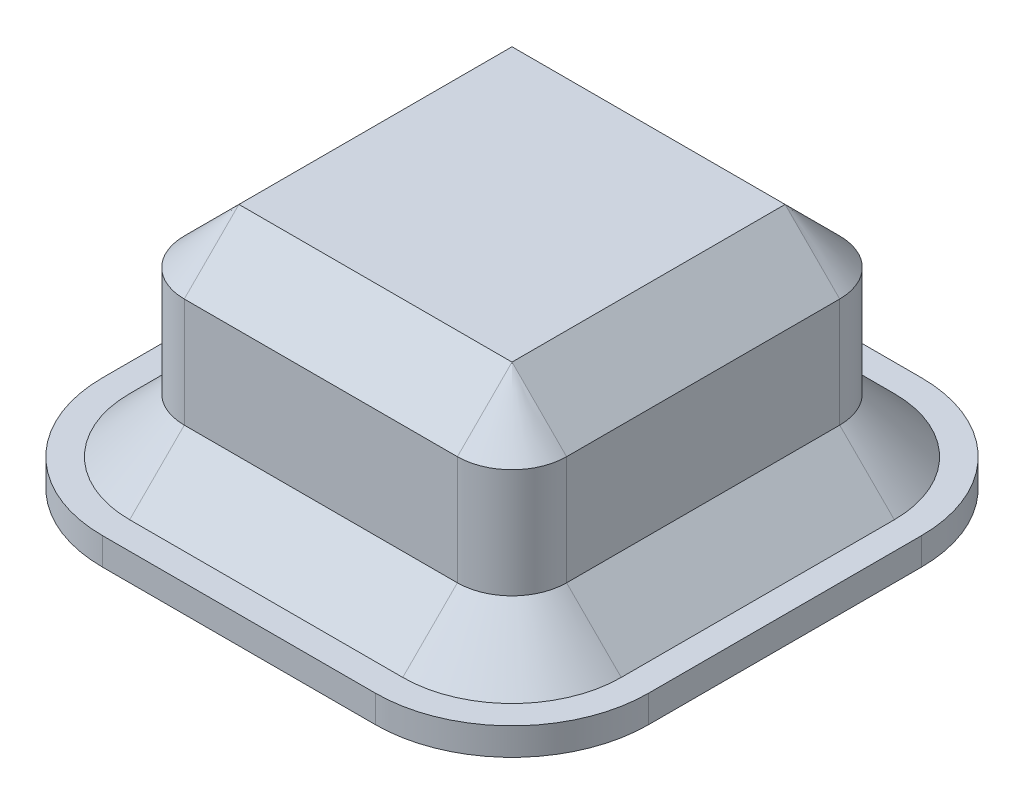
SolidWorks part; units mm, degrees
material "ABS"
ref_plane "Front Plane" through (0, 0, 0) normal (0, 0, 1) x (1, 0, 0)
ref_plane "Top Plane" through (0, 0, 0) normal (0, 1, 0) x (1, 0, 0)
ref_plane "Right Plane" through (0, 0, 0) normal (1, 0, 0) x (0, 0, -1)
sketch "Sketch1" plane through (0, 0, 0) normal (0, 1, 0) x (1, 0, 0)
  line L1 (-10, 10) -> (10, 10)
  line L2 (-10, 10) -> (-10, -10)
  line L3 (-10, -10) -> (10, -10)
  line L4 (10, 10) -> (10, -10)
  line L5 (-10, 10) -> (10, -10) construction
  line L6 (-10, -10) -> (10, 10) construction
  point P0 (0, 0)
  dimension "D1" = 20
  dimension "D2" = 20
extrude "Boss-Extrude1" add sketch "Sketch1" along normal blind 1
fillet "Fillet2" radius 5 4 edges at (-10, 0.5, 10) (-10, 0.5, -10) (10, 0.5, -10) (10, 0.5, 10)
sketch "Sketch3" plane through (0, 1, 0) normal (0, 1, 0) x (1, 0, 0)
  line L0 (-7, 5) -> (-7, -5)
  line L1 (-5, -7) -> (5, -7)
  line L2 (7, -5) -> (7, 5)
  line L3 (5, 7) -> (-5, 7)
  line L4 (-10, 5) -> (-10, -5)
  line L5 (-5, -10) -> (5, -10)
  line L6 (10, -5) -> (10, 5)
  line L7 (5, 10) -> (-5, 10)
  line L8 (-10, 5) -> (-10, -5)
  line L9 (-5, -10) -> (5, -10)
  line L10 (10, -5) -> (10, 5)
  line L11 (5, 10) -> (-5, 10)
  arc A0 (-7, -5) -> (-5, -7) centre (-5, -5) ccw
  arc A1 (5, -7) -> (7, -5) centre (5, -5) ccw
  arc A2 (7, 5) -> (5, 7) centre (5, 5) ccw
  arc A3 (-5, 7) -> (-7, 5) centre (-5, 5) ccw
  arc A4 (-10, -5) -> (-5, -10) centre (-5, -5) ccw
  arc A5 (5, -10) -> (10, -5) centre (5, -5) ccw
  arc A6 (10, 5) -> (5, 10) centre (5, 5) ccw
  arc A7 (-5, 10) -> (-10, 5) centre (-5, 5) ccw
  arc A8 (-10, -5) -> (-5, -10) centre (-5, -5) ccw
  arc A9 (5, -10) -> (10, -5) centre (5, -5) ccw
  arc A10 (10, 5) -> (5, 10) centre (5, 5) ccw
  arc A11 (-5, 10) -> (-10, 5) centre (-5, 5) ccw
  dimension "D1" = 0
  dimension "D2" = 3
extrude "Boss-Extrude3" add sketch "Sketch3" along normal blind 8 contours L0 A0 L1 A1 L2 A2 L3 A3
chamfer "Chamfer1" distance 2 angle 45 8 edges at (6.4142, 1, 6.4142) (7, 1, 0) (6.4142, 1, -6.4142) (0, 1, -7) (-6.4142, 1, -6.4142) (0, 1, 7) (-6.4142, 1, 6.4142) (-7, 1, 0)
chamfer "Chamfer3" distance 2 angle 45 8 edges at (-6.4142, 9, -6.4142) (0, 9, -7) (6.4142, 9, -6.4142) (7, 9, 0) (6.4142, 9, 6.4142) (-7, 9, 0) (-6.4142, 9, 6.4142) (0, 9, 7)
